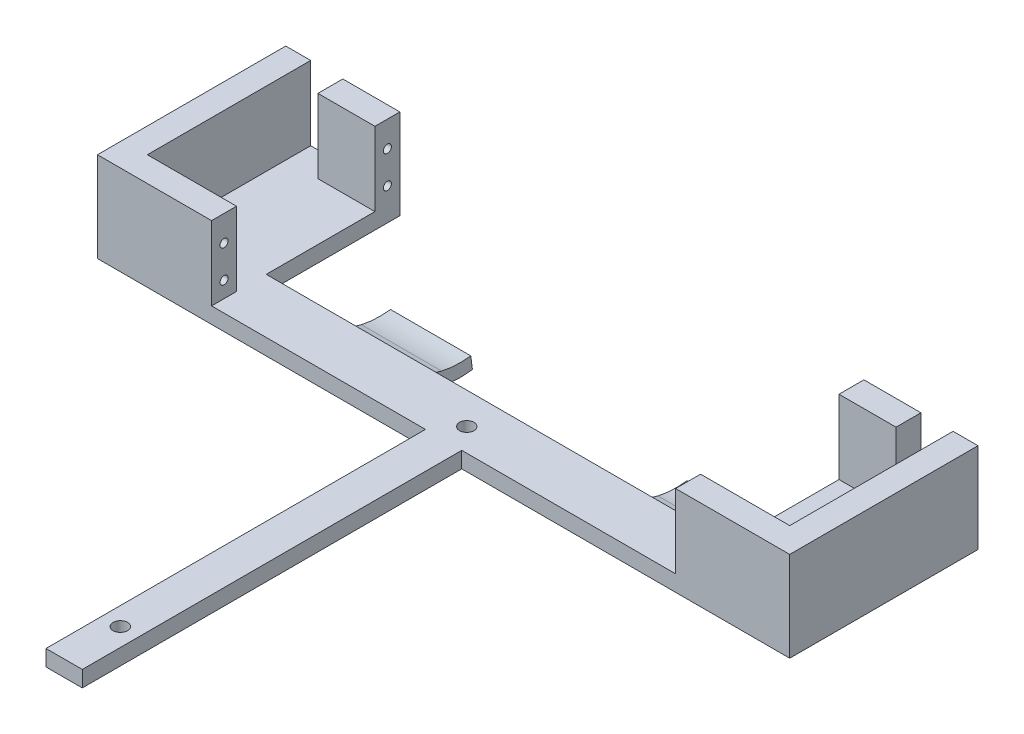
SolidWorks part; units mm, degrees
material "ABS"
ref_plane "Front" through (0, 0, 0) normal (0, 0, 1) x (1, 0, 0)
ref_plane "Top" through (0, 0, 0) normal (0, 1, 0) x (1, 0, 0)
ref_plane "Right" through (0, 0, 0) normal (1, 0, 0) x (0, 0, -1)
sketch "Sketch5" plane through (0, 0, 0) normal (0, 1, 0) x (1, 0, 0)
  line L0 (-7.71, -30) -> (-7.71, 88.14)
  line L5 (-109.82, 146.76) -> (-74.3, 146.76)
  line L6 (-74.3, 146.76) -> (-74.3, 105.16)
  line L19 (-2.06, -30) -> (-2.06, 105.16) construction
  line L21 (-7.71, 88.14) -> (-109.82, 88.14)
  line L22 (-109.82, 88.14) -> (-109.82, 146.76)
  line L29 (-74.3, 105.16) -> (-2.06, 105.16)
  line L30 (-2.06, 105.16) -> (-2.06, -30)
  line L31 (-2.06, -30) -> (-7.71, -30)
  circle A0 centre (-2.06, -12.52) radius 2.25
  circle A1 centre (-2.06, 95.35) radius 2.25
  dimension "D6" = 4.5
  dimension "D1" = 35.52
  dimension "D2" = 5.65
  dimension "D3" = 41.6
  dimension "D4" = 58.62
  dimension "D5" = 17.48
  dimension "D7" = 125.35
  dimension "D8" = 66.59
  dimension "D9" = 118.14
extrude "Boss-Extrude1" add sketch "Sketch5" along normal blind 5 contours A1 L30 L29 L6 L5 L22 L21 L0 L31 A0 region at (-61.0204, 0, -96.4176)
sketch "Sketch7" plane through (0, 5, 0) normal (0, 1, 0) x (1, 0, 0)
  line L0 (-109.82, 146.76) -> (-109.82, 88.14)
  line L1 (-109.82, 88.14) -> (-74.3, 88.14)
  line L2 (-7.71, 88.14) -> (-109.82, 88.14) construction
  line L3 (-74.3, 88.14) -> (-74.3, 95.9)
  line L4 (-74.3, 95.9) -> (-102.06, 95.9)
  line L5 (-102.06, 95.9) -> (-102.06, 146.76)
  line L6 (-109.82, 146.76) -> (-74.3, 146.76) construction
  line L7 (-102.06, 146.76) -> (-109.82, 146.76)
  line L9 (-74.3, 146.76) -> (-92.06, 146.76)
  line L10 (-74.3, 146.76) -> (-74.3, 139)
  line L11 (-74.3, 139) -> (-92.06, 139)
  line L12 (-92.06, 146.76) -> (-92.06, 139)
  dimension "D1" = 7.76
  dimension "D2" = 7.76
  dimension "D3" = 35.52
  dimension "D4" = 17.76
  dimension "D5" = 7.76
extrude "Boss-Extrude2" add sketch "Sketch7" along normal blind 23
sketch "Sketch8" plane through (-74.3, 0, 0) normal (1, 0, 0) x (0, 0, -1)
  line L1 (88.14, 5) -> (95.9, 5) construction
  line L2 (88.14, 6.6877) -> (95.9, 6.6877) construction
  line L3 (88.14, 28) -> (88.14, 5) construction
  line L4 (95.9, 28) -> (95.9, 5) construction
  line L5 (139, 8.1897) -> (146.76, 8.1897) construction
  line L6 (139, 28) -> (139, 5) construction
  line L7 (146.76, 28) -> (146.76, 0) construction
  line L8 (139, 5) -> (105.16, 5) construction
  circle A0 centre (92.02, 10) radius 1.25
  circle A1 centre (92.02, 20) radius 1.25
  circle A2 centre (142.88, 10) radius 1.25
  circle A3 centre (142.88, 20) radius 1.25
  point P12 (92.02, 6.6877)
  point P23 (142.88, 8.1897)
  dimension "D1" = 2.5
  dimension "D2" = 5
  dimension "D3" = 15
  dimension "D4" = 5
  dimension "D5" = 15
extrude "Cut-Extrude1" cut sketch "Sketch8" against normal blind 5
mirror "Mirror2" about plane through (-2.06, 5, 0) normal (1, 0, 0) of "Boss-Extrude1", "Boss-Extrude2"
ref_plane "Plane3" through (-2.06, 0, 0) normal (1, 0, 0) x (0, 0, -1)
sketch "Sketch9" plane through (70.18, 0, 0) normal (-1, 0, 0) x (0, 0, 1)
  line L0 (-146.76, 10.6093) -> (-139, 10.6093) construction
  line L1 (-146.76, 28) -> (-146.76, 0) construction
  line L2 (-139, 28) -> (-139, 5) construction
  line L3 (-139, 5) -> (-105.16, 5) construction
  line L4 (-95.9, 28) -> (-95.9, 5) construction
  line L5 (-95.9, 10.6093) -> (-88.14, 10.6093) construction
  line L6 (-88.14, 28) -> (-88.14, 5) construction
  circle A0 centre (-142.88, 10) radius 1.25
  circle A1 centre (-142.88, 20) radius 1.25
  circle A2 centre (-92.02, 10) radius 1.25
  circle A3 centre (-92.02, 20) radius 1.25
  point P6 (-142.88, 10.6093)
  point P13 (-92.02, 10.6093)
  dimension "D3" = 2.5
  dimension "D1" = 5
  dimension "D2" = 15
  dimension "D4" = 5
  dimension "D5" = 15
extrude "Cut-Extrude2" cut sketch "Sketch9" against normal blind 5
sketch "Sketch10" plane through (0, 5, 0) normal (0, 1, 0) x (1, 0, 0)
  line L0 (-60.7286, 88.14) -> (-60.7286, 139.4308) construction
  line L1 (-7.71, 88.14) -> (-74.3, 88.14) construction
ref_plane "Plane4" through (-60.7286, 0, 0) normal (1, 0, 0) x (0, 0, -1)
ref_plane "Plane5" through (-74.3, 5, -95.9) normal (0, -1, 0) x (-1, 0, 0)
sketch "Sketch12" plane through (-60.7286, 0, 0) normal (1, 0, 0) x (0, 0, -1)
  line L0 (113.9225, 28.04) -> (139.9225, 2.04) construction
  line L1 (139.9225, 28.04) -> (113.9225, 28.04)
  line L2 (139.9225, 28.04) -> (139.9225, 2.04)
  line L3 (139.9225, 2.04) -> (113.9225, 2.04)
  line L4 (113.9225, 28.04) -> (113.9225, 2.04)
  line L5 (130.2681, -10.2396) -> (130.7929, -14.205)
  line L6 (103.4821, 5) -> (99.1835, 5)
  line L7 (103.4821, 5) -> (150.3628, 5) construction
  line L8 (126.9225, 15.04) -> (130.2681, -10.2396) construction
  line L9 (126.9225, 15.04) -> (126.9225, 5) construction
  circle A0 centre (126.9225, 15.04) radius 13
  circle A1 centre (126.9225, 15.04) radius 23.5
  circle A2 centre (126.9225, 15.04) radius 25.5
  circle A3 centre (126.9225, 15.04) radius 29.5
  dimension "D3" = 10.04
extrude "Boss-Extrude3" add sketch "Sketch12" along normal blind 25 contours L6 A3 L5 A2 region at (-60.7286, -6.9865, -113.9235)
mirror "Mirror3" about plane through (-2.06, 0, 0) normal (1, 0, 0) of "Boss-Extrude3"
fillet "Fillet1" radius 22 2 edges at (-48.2286, 1.7492, -105.16) (44.1086, 1.7492, -105.16)
fillet "Fillet2" radius 30 2 edges at (-48.2286, 0, -101.5443) (44.1086, 0, -101.5443)
ref_plane "Plane6" through (0, 0, -117.45) normal (0, 0, 1) x (1, 0, 0)
